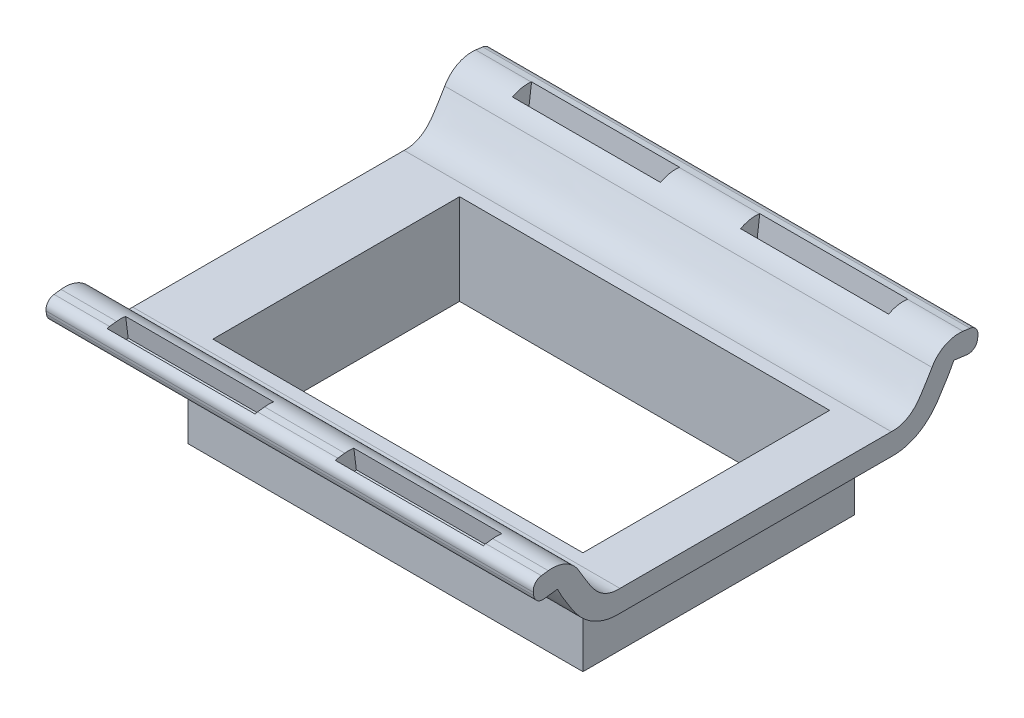
SolidWorks part; units mm, degrees
ref_plane "Front Plane" through (0, 0, 0) normal (0, 0, 1) x (1, 0, 0)
ref_plane "Top Plane" through (0, 0, 0) normal (0, 1, 0) x (1, 0, 0)
ref_plane "Right Plane" through (0, 0, 0) normal (1, 0, 0) x (0, 0, -1)
sketch "Sketch1" plane through (0, 0, 0) normal (0, 1, 0) x (1, 0, 0)
  line L0 (-45.0588, 34.7647) -> (-45.0588, -9.2353)
  line L1 (-43.0588, 32.7647) -> (16.9412, 32.7647)
  line L2 (-43.0588, 32.7647) -> (-43.0588, -7.2353)
  line L3 (-43.0588, -7.2353) -> (16.9412, -7.2353)
  line L4 (16.9412, 32.7647) -> (16.9412, -7.2353)
  line L5 (-43.0588, 32.7647) -> (16.9412, -7.2353) construction
  line L6 (-43.0588, -7.2353) -> (16.9412, 32.7647) construction
  line L7 (-45.0588, -9.2353) -> (18.9412, -9.2353)
  line L8 (18.9412, 34.7647) -> (18.9412, -9.2353)
  line L9 (-45.0588, 34.7647) -> (18.9412, 34.7647)
  point P0 (-13.0588, 12.7647)
  dimension "D1" = 60
  dimension "D2" = 40
  dimension "D3" = 2
ref_plane "Plane1" through (18.9412, 0, 0) normal (1, 0, 0) x (0, 0, -1)
sketch "Sketch2" plane through (18.9412, 0, 0) normal (1, 0, 0) x (0, 0, -1)
  line L0 (-9.2353, 0) -> (34.7647, 0)
  line L1 (34.7647, 0) -> (-9.2353, 0) construction
  line L2 (34.7647, 0) -> (-9.2353, 0) construction
  line L3 (12.7647, 0) -> (12.7647, 19.5531) construction
  line L5 (42.3885, 14.3568) -> (-16.859, 14.3568) construction
  line L9 (-11.3396, -3.5) -> (36.3638, -3.5)
  line L12 (-20.621, 14.3568) -> (-20.7592, 14.3568)
  line L13 (-17.7913, 8.6496) -> (-17.7913, 8.6496) construction
  line L14 (-16.859, 14.3568) -> (-20.1995, 11.1894) construction
  line L15 (42.3885, 14.3568) -> (42.3885, 8.8037) construction
  line L16 (45.8885, 14.3568) -> (45.8885, 7.4989) construction
  line L17 (-20.3312, 8.3632) -> (-16.859, 8.8037)
  line L18 (45.8606, 8.3632) -> (42.3885, 8.8037)
  line L19 (42.3885, 8.8037) -> (34.7647, 0) construction
  line L20 (45.8885, 7.4989) -> (36.3638, -3.5) construction
  line L21 (-16.859, 14.3568) -> (-9.2353, 0) construction
  line L22 (-17.7913, 8.6496) -> (-11.3396, -3.5) construction
  line L23 (-19.8906, 4.891) -> (-19.3719, 4.9568)
  line L24 (-9.1587, -3.5) -> (34.6881, -3.5)
  line L25 (45.42, 4.891) -> (44.9013, 4.9568)
  line L26 (-20.3312, 8.3632) -> (-21.9796, 8.154)
  line L27 (-23.2789, 6.4771) -> (-23.2159, 5.9811)
  line L28 (-19.8906, 4.891) -> (-21.539, 4.6818)
  line L29 (45.42, 4.891) -> (47.0684, 4.6818)
  line L30 (48.8083, 6.4771) -> (48.7453, 5.9811)
  line L31 (45.8606, 8.3632) -> (47.509, 8.154)
  arc A4 (-21.539, 4.6818) -> (-23.2159, 5.9811) centre (-21.7278, 6.1699) cw
  arc A5 (-21.9796, 8.154) -> (-23.2789, 6.4771) centre (-21.7908, 6.6659) ccw
  arc A6 (47.0684, 4.6818) -> (48.7453, 5.9811) centre (47.2573, 6.1699) ccw
  arc A7 (47.509, 8.154) -> (48.8083, 6.4771) centre (47.3202, 6.6659) cw
  spline S0 degree 3 poles (42.3885, 8.8037) (42.2414, 7.6451) (42.0055, 6.983) (41.1949, 5.3673) (40.6762, 4.5691) (39.7486, 3.1038) (38.6266, 1.2021) (36.4877, -0.0862) (34.7647, 0) knots 0.100937 0.100937 0.100937 0.100937 0.214702 0.247771 0.411203 0.4592 0.679739 1 1 1 1
  spline S1 degree 3 poles (-16.859, 8.8037) (-16.712, 7.6451) (-16.4761, 6.983) (-15.6654, 5.3673) (-15.1468, 4.5691) (-14.2192, 3.1038) (-13.0972, 1.2021) (-10.9583, -0.0862) (-9.2353, 0) knots 0.100937 0.100937 0.100937 0.100937 0.214702 0.247771 0.411203 0.4592 0.679739 1 1 1 1
  spline S2 degree 1 poles (-19.3719, 4.9568) (-9.1587, -3.5) knots 0 0 1 1 construction
  spline S3 degree 1 poles (44.9013, 4.9568) (34.6881, -3.5) knots 0 0 1 1 construction
  spline S4 degree 3 poles (-19.3719, 4.9568) (-19.2991, 4.8056) (-19.1435, 4.4955) (-18.861, 3.9612) (-18.3799, 3.1173) (-17.8088, 2.2383) (-17.2679, 1.3606) (-16.5056, 0.1706) (-15.3729, -1.1679) (-13.787, -2.4192) (-12.0345, -3.1864) (-10.4372, -3.4868) (-9.5799, -3.5164) (-9.1587, -3.5) knots 0.220067 0.220067 0.220067 0.220067 0.244324 0.268581 0.317096 0.414125 0.511154 0.608184 0.705213 0.802242 0.899272 0.947786 0.996301 0.996301 0.996301 0.996301
  spline S5 degree 3 poles (34.6881, -3.5) (35.1093, -3.5164) (35.9666, -3.4868) (37.5639, -3.1864) (39.3164, -2.4192) (40.9023, -1.1679) (42.035, 0.1706) (42.7973, 1.3606) (43.3382, 2.2383) (43.9094, 3.1173) (44.3904, 3.9612) (44.673, 4.4955) (44.8285, 4.8056) (44.9013, 4.9568) knots 0.220067 0.220067 0.220067 0.220067 0.268581 0.317096 0.414125 0.511154 0.608184 0.705213 0.802242 0.899272 0.947786 0.972044 0.996301 0.996301 0.996301 0.996301
  dimension "D1" = 3.5
  dimension "D2" = 3.5
  dimension "D3" = 1.5
extrude "Boss-Extrude1" add sketch "Sketch2" against normal blind 73 and the other way blind 6 contours L9 S5 L25 L29 A6 L30 A7 L31 L18 S0 L0 S1 L17 L26 A5 L27 A4 L28 L23 S4 region at (18.9412, -0.7315, -12.7647)
extrude "Cut-Extrude2" cut sketch "Sketch1" against normal blind 10 contours L4 L1 L2 L3 region at (-13.0588, 0, -12.7647)
sketch "Sketch5" plane through (0, 7.2974, 0.926) normal (0, -0.992, -0.1259) x (1, 0, 0)
  line L0 (-54.0588, 19.6861) -> (-45.0588, 19.6861) construction
  line L1 (-54.0588, 18.5939) -> (-54.0588, 20.7784) construction
  line L2 (-14.5588, 20.7784) -> (-14.5588, 5.5792) construction
  line L3 (24.9412, 20.7784) -> (-54.0588, 20.7784) construction
  line L4 (24.9412, 19.6861) -> (15.9412, 19.6861) construction
  line L5 (-45.0588, 18.1861) -> (-45.0588, 21.1861)
  line L6 (-45.0588, 21.1861) -> (-21.0588, 21.1861)
  line L7 (-21.0588, 21.1861) -> (-21.0588, 18.1861)
  line L8 (-21.0588, 18.1861) -> (-45.0588, 18.1861)
  line L9 (-8.0588, 21.1861) -> (-8.0588, 18.1861)
  line L10 (15.9412, 21.1861) -> (-8.0588, 21.1861)
  line L11 (15.9412, 18.1861) -> (15.9412, 21.1861)
  line L12 (-8.0588, 18.1861) -> (15.9412, 18.1861)
  line L13 (-54.0588, -12.2226) -> (28.6581, -12.2226) construction
  line L14 (-54.0588, 10.1923) -> (-54.0588, -34.6374) construction
  line L15 (-8.0588, -42.6313) -> (15.9412, -42.6313)
  line L16 (15.9412, -42.6313) -> (15.9412, -45.6313)
  line L17 (15.9412, -45.6313) -> (-8.0588, -45.6313)
  line L18 (-8.0588, -45.6313) -> (-8.0588, -42.6313)
  line L19 (-21.0588, -42.6313) -> (-45.0588, -42.6313)
  line L20 (-21.0588, -45.6313) -> (-21.0588, -42.6313)
  line L21 (-45.0588, -45.6313) -> (-21.0588, -45.6313)
  line L22 (-45.0588, -42.6313) -> (-45.0588, -45.6313)
  point P13 (-45.0588, 19.6861)
  point P14 (-45.0588, 19.6861)
  point P32 (-45.0588, -44.1313)
sketch "Sketch7" plane through (0, -3.5, 0) normal (0, -1, 0) x (1, 0, 0)
  line L0 (-43.0588, 7.2353) -> (16.9412, 7.2353)
  line L1 (16.9412, 7.2353) -> (16.9412, -32.7647)
  line L2 (16.9412, -32.7647) -> (-43.0588, -32.7647)
  line L3 (-43.0588, -32.7647) -> (-43.0588, 7.2353)
  line L4 (-45.0588, 9.2353) -> (18.9412, 9.2353)
  line L5 (18.9412, 9.2353) -> (18.9412, -34.7647)
  line L6 (18.9412, -34.7647) -> (-45.0588, -34.7647)
  line L7 (-45.0588, -34.7647) -> (-45.0588, 9.2353)
extrude "Boss-Extrude2" add sketch "Sketch7" along normal blind 11.2
extrude "Cut-Extrude3" cut sketch "Sketch5" against normal blind 11.2 contours L8 L5 L6 L7 | L12 L11 L10 L9
sketch "Sketch8" plane through (0, 13.9576, -1.7711) normal (0, 0.992, -0.1259) x (1, 0, 0)
  line L0 (-54.0588, 43.5239) -> (-45.0588, 43.5239) construction
  line L1 (24.9412, 43.5239) -> (15.9412, 43.5239) construction
  line L2 (-45.0588, 42.0239) -> (-45.0588, 45.0239)
  line L3 (-45.0588, 45.0239) -> (-21.0588, 45.0239)
  line L4 (-21.0588, 45.0239) -> (-21.0588, 42.0239)
  line L5 (-21.0588, 42.0239) -> (-45.0588, 42.0239)
  line L6 (-8.0588, 45.0239) -> (-8.0588, 42.0239)
  line L7 (15.9412, 45.0239) -> (-8.0588, 45.0239)
  line L8 (15.9412, 42.0239) -> (15.9412, 45.0239)
  line L9 (-8.0588, 42.0239) -> (15.9412, 42.0239)
  point P7 (-45.0588, 43.5239)
  point P8 (-45.0588, 43.5239)
extrude "Cut-Extrude4" cut sketch "Sketch8" against normal blind 11.2
fillet "Fillet1" radius 5 2 edges at (-14.5588, 8.8037, -42.3885) (-14.5588, 8.8037, 16.859)
